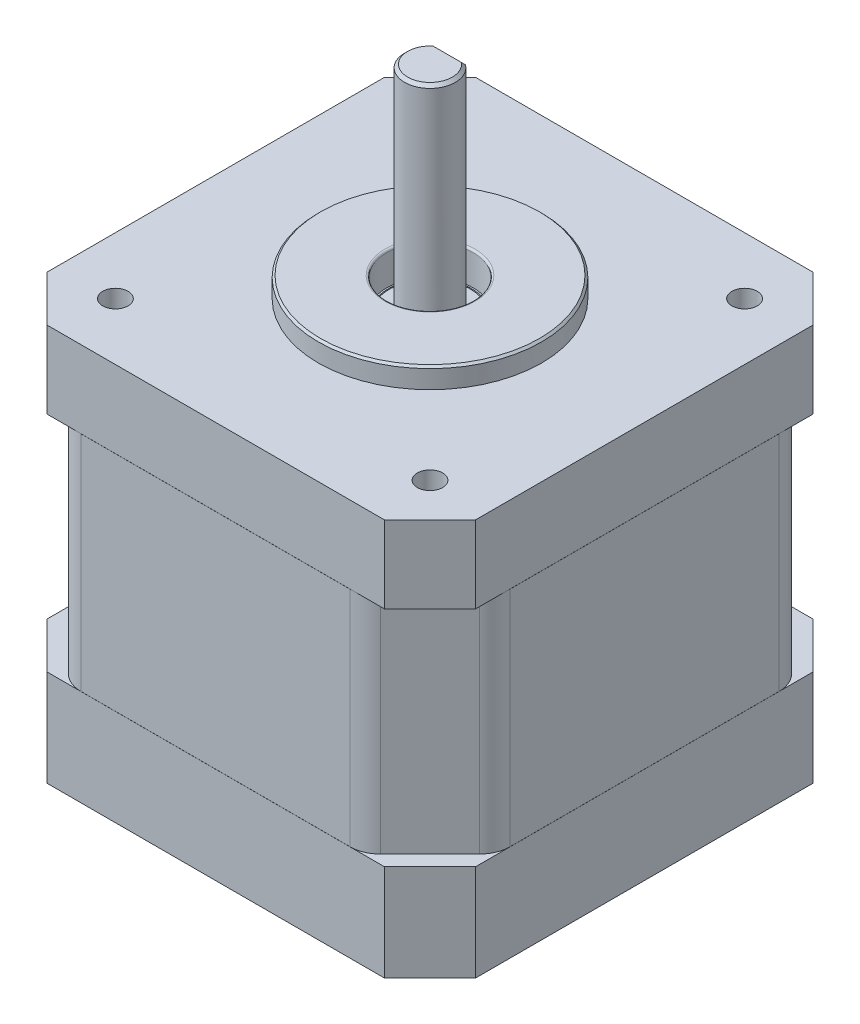
SolidWorks part; units mm, degrees
other "Cámara1"
material "Acero al carbono fundido"
ref_plane "Alzado" through (0, 0, 0) normal (0, 0, 1) x (1, 0, 0)
ref_plane "Planta" through (0, 0, 0) normal (0, 1, 0) x (1, 0, 0)
ref_plane "Vista lateral" through (0, 0, 0) normal (1, 0, 0) x (0, 0, -1)
sketch "Croquis1" plane through (0, 0, 0) normal (0, 1, 0) x (1, 0, 0)
  line L0 (-21.125, 16.625) -> (-16.625, 21.125)
  line L1 (-16.625, -21.125) -> (16.625, -21.125)
  line L2 (-21.125, -16.625) -> (-21.125, 16.625)
  line L3 (-16.625, 21.125) -> (16.625, 21.125)
  line L4 (21.125, -16.625) -> (21.125, 16.625)
  line L5 (-21.125, -21.125) -> (21.125, 21.125) construction
  line L6 (-21.125, 21.125) -> (21.125, -21.125) construction
  line L7 (16.625, 21.125) -> (21.125, 16.625)
  line L8 (-21.125, -16.625) -> (-16.625, -21.125)
  line L9 (16.625, -21.125) -> (21.125, -16.625)
  circle A0 centre (-15.5, 15.5) radius 1
  circle A1 centre (15.5, 15.5) radius 1
  circle A2 centre (-15.5, -15.5) radius 1
  circle A3 centre (15.5, -15.5) radius 1
  point P0 (0, 0)
  dimension "D3" = 2
  dimension "D4" = 31
  dimension "D5" = 31
  dimension "D1" = 42.25
  dimension "D2" = 42.25
extrude "Saliente-Extruir1" add sketch "Croquis1" along normal blind 7.6
sketch "Croquis2" plane through (0, 7.6, 0) normal (0, 1, 0) x (1, 0, 0)
  circle A0 centre (0, 0) radius 11
  dimension "D1" = 22
extrude "Saliente-Extruir2" add sketch "Croquis2" along normal blind 2
chamfer "Chaflán1" distance 0.2 angle 45 1 edges at (0, 9.6, 11)
sketch "Croquis3" plane through (0, 9.6, 0) normal (0, 1, 0) x (1, 0, 0)
  circle A0 centre (0, 0) radius 4.25
  dimension "D1" = 8.5
extrude "Cortar-Extruir1" cut sketch "Croquis3" against normal blind 3.2
fillet "Redondeo1" radius 0.2 1 edges at (0, 9.6, 4.25)
sketch "Croquis4" plane through (0, 6.4, 0) normal (0, 1, 0) x (1, 0, 0)
  circle A0 centre (0, 0) radius 4.1
  circle A1 centre (0, 0) radius 4
  dimension "D1" = 8.2
  dimension "D2" = 8
extrude "Cortar-Extruir2" cut sketch "Croquis4" against normal blind 0.5
sketch "Croquis5" plane through (0, 6.4, 0) normal (0, 1, 0) x (1, 0, 0)
  circle A0 centre (0, 0) radius 2.5
  dimension "D1" = 5
extrude "Saliente-Extruir3" add sketch "Croquis5" along normal blind 21.2
chamfer "Chaflán2" distance 0.3 angle 45 1 edges at (0, 27.6, 2.5)
sketch "Croquis7" plane through (0, 27.6, 0) normal (0, 1, 0) x (1, 0, 0)
  line L0 (0, -2.5) -> (0, 2) construction
  line L1 (-1.5, 2) -> (1.5, 2)
  circle A0 centre (0, 0) radius 2.5 construction
  circle A1 centre (0, 0) radius 2.5 construction
  arc A2 (1.5, 2) -> (-1.5, 2) centre (0, 0) ccw
  point P11 (0, 2)
  dimension "D1" = 4.5
extrude "Cortar-Extruir4" cut sketch "Croquis7" against normal blind 17.2
fillet "Redondeo2" radius 0.1 1 edges at (0, 10.4, -2)
chamfer "Chaflán3" distance 0.3 angle 45 1 edges at (0, 27.6, -2)
sketch "Croquis8" plane through (0, 0, 0) normal (0, -1, 0) x (1, 0, 0)
  line L0 (-14.5, 21.125) -> (14.5, 21.125)
  line L1 (-16.625, 21.125) -> (16.625, 21.125) construction
  line L2 (0, 21.125) -> (0, 0) construction
  line L3 (0, 0) -> (-21.125, 0) construction
  line L4 (-21.125, -16.625) -> (-21.125, 16.625) construction
  line L5 (-21.125, -14.5) -> (-21.125, 14.5)
  line L6 (-21.125, 14.5) -> (-14.5, 21.125)
  line L7 (21.125, -14.5) -> (21.125, 14.5)
  line L8 (-14.5, -21.125) -> (14.5, -21.125)
  line L9 (-21.125, -14.5) -> (-14.5, -21.125)
  line L10 (14.5, -21.125) -> (21.125, -14.5)
  line L11 (21.125, 14.5) -> (14.5, 21.125)
  point P5 (0, 21.125)
  point P14 (-21.125, 0)
  dimension "D1" = 29
  dimension "D2" = 29
extrude "Saliente-Extruir4" add sketch "Croquis8" along normal blind 22
sketch "Croquis9" plane through (0, -22, 0) normal (0, -1, 0) x (1, 0, 0)
  line L8 (16.625, 21.125) -> (-16.625, 21.125)
  line L9 (21.125, 16.625) -> (16.625, 21.125)
  line L10 (21.125, -16.625) -> (21.125, 16.625)
  line L11 (16.625, -21.125) -> (21.125, -16.625)
  line L12 (-16.625, -21.125) -> (16.625, -21.125)
  line L13 (-21.125, -16.625) -> (-16.625, -21.125)
  line L14 (-21.125, 16.625) -> (-21.125, -16.625)
  line L15 (-16.625, 21.125) -> (-21.125, 16.625)
  line L16 (16.625, 21.125) -> (-16.625, 21.125)
  line L17 (21.125, 16.625) -> (16.625, 21.125)
  line L18 (21.125, -16.625) -> (21.125, 16.625)
  line L19 (16.625, -21.125) -> (21.125, -16.625)
  line L20 (-16.625, -21.125) -> (16.625, -21.125)
  line L21 (-21.125, -16.625) -> (-16.625, -21.125)
  line L22 (-21.125, 16.625) -> (-21.125, -16.625)
  line L23 (-16.625, 21.125) -> (-21.125, 16.625)
  dimension "D5" = 0
extrude "Saliente-Extruir5" add sketch "Croquis9" along normal blind 9.5
sketch "Croquis10" plane through (0, -31.5, 0) normal (0, -1, 0) x (1, 0, 0)
  line L0 (-8.175, -21.125) -> (8.175, -21.125)
  line L1 (-16.625, -21.125) -> (16.625, -21.125) construction
  line L2 (0, 0) -> (0, -21.125) construction
  line L3 (8.175, -21.125) -> (8.175, -25.125)
  line L4 (8.175, -25.125) -> (-8.175, -25.125)
  line L5 (-8.175, -25.125) -> (-8.175, -21.125)
  point P5 (0, -21.125)
  dimension "D1" = 16.35
  dimension "D2" = 4
extrude "Saliente-Extruir6" add sketch "Croquis10" against normal blind 3.3
sketch "Croquis11" plane through (0, 6.4, 0) normal (0, 1, 0) x (1, 0, 0)
  circle A0 centre (0, 0) radius 2.575
  circle A1 centre (0, 0) radius 2.5 construction
  circle A2 centre (0, 0) radius 2.5
  dimension "D1" = 5.15
extrude "Cortar-Extruir5" cut sketch "Croquis11" against normal up to surface (0.5 mm away) up to face at (0, 5.9, 4)
sketch "Croquis12" plane through (0, -28.2, 0) normal (0, 1, 0) x (1, 0, 0)
  line L0 (-7, 21.125) -> (7, 21.125)
  line L1 (16.625, 21.125) -> (-16.625, 21.125) construction
  line L2 (-7, 21.125) -> (-7, 25.825)
  line L3 (-7, 25.825) -> (7, 25.825)
  line L4 (7, 25.825) -> (7, 21.125)
  point P5 (0, 21.125)
  dimension "D1" = 14
  dimension "D2" = 4.7
extrude "Saliente-Extruir7" add sketch "Croquis12" along normal blind 1
sketch "Croquis13" plane through (0, -27.2, 0) normal (0, 1, 0) x (1, 0, 0)
  line L0 (16.625, 21.125) -> (-16.625, 21.125) construction
  line L1 (-7.6, 21.125) -> (7.6, 21.125)
  line L2 (7.6, 21.125) -> (7.6, 27.625)
  line L3 (7.6, 27.625) -> (-7.6, 27.625)
  line L4 (-7.6, 27.625) -> (-7.6, 21.125)
  point P0 (0, 21.125)
  point P6 (0, 21.125)
  dimension "D1" = 15.2
  dimension "D2" = 6.5
extrude "Saliente-Extruir8" add sketch "Croquis13" along normal blind 5.5
sketch "Croquis14" plane through (0, 0, -27.625) normal (0, 0, -1) x (-1, 0, 0)
  line L4 (0, -22.7) -> (0, -21.7) construction
  line L5 (7.6, -21.7) -> (-7.6, -21.7) construction
  line L6 (4, -22.7) -> (4, -21.7)
  line L7 (-4, -22.7) -> (-4, -21.7)
  line L8 (-6.6, -26.2) -> (6.6, -26.2)
  line L9 (6.6, -26.2) -> (6.6, -22.7)
  line L10 (6.6, -22.7) -> (-6.6, -22.7)
  line L11 (-6.6, -22.7) -> (-6.6, -26.2)
  line L12 (-6.6, -26.2) -> (6.6, -26.2)
  line L13 (6.6, -26.2) -> (6.6, -22.7)
  line L14 (6.6, -22.7) -> (4, -22.7)
  line L15 (-6.6, -22.7) -> (-6.6, -26.2)
  line L16 (-7.6, -21.7) -> (7.6, -21.7) construction
  line L20 (-4, -21.7) -> (4, -21.7)
  line L21 (-4, -22.7) -> (-6.6, -22.7)
  point P1 (0, -22.7)
  dimension "D2" = 4
  dimension "D1" = 1
  dimension "D3" = 4
extrude "Cortar-Extruir6" cut sketch "Croquis14" against normal blind 4.1
sketch "Croquis15" plane through (0, 0, -23.525) normal (0, 0, -1) x (-1, 0, 0)
  line L0 (-6.6, -24.45) -> (6.6, -24.45) construction
  line L1 (-6.6, -22.7) -> (-6.6, -26.2) construction
  line L2 (6.6, -26.2) -> (6.6, -22.7) construction
  line L3 (-3.0743, -24.2) -> (-2.5743, -24.2)
  line L4 (-4.9643, -24.7) -> (-4.4643, -24.7)
  line L5 (-4.9643, -24.7) -> (-4.9643, -24.2)
  line L6 (-4.9643, -24.2) -> (-4.4643, -24.2)
  line L7 (-4.4643, -24.7) -> (-4.4643, -24.2)
  line L8 (-4.9643, -24.7) -> (-4.4643, -24.2) construction
  line L9 (-4.9643, -24.2) -> (-4.4643, -24.7) construction
  line L10 (-2.5743, -24.7) -> (-2.5743, -24.2)
  line L11 (-3.0743, -24.7) -> (-2.5743, -24.7)
  line L12 (-3.0743, -24.7) -> (-3.0743, -24.2)
  line L13 (-1.1843, -24.2) -> (-0.6843, -24.2)
  line L14 (-0.6843, -24.7) -> (-0.6843, -24.2)
  line L15 (-1.1843, -24.7) -> (-0.6843, -24.7)
  line L16 (-1.1843, -24.7) -> (-1.1843, -24.2)
  line L17 (0.7057, -24.2) -> (1.2057, -24.2)
  line L18 (1.2057, -24.7) -> (1.2057, -24.2)
  line L19 (0.7057, -24.7) -> (1.2057, -24.7)
  line L20 (0.7057, -24.7) -> (0.7057, -24.2)
  line L21 (2.5957, -24.2) -> (3.0957, -24.2)
  line L22 (3.0957, -24.7) -> (3.0957, -24.2)
  line L23 (2.5957, -24.7) -> (3.0957, -24.7)
  line L24 (2.5957, -24.7) -> (2.5957, -24.2)
  line L25 (4.4857, -24.2) -> (4.9857, -24.2)
  line L26 (4.9857, -24.7) -> (4.9857, -24.2)
  line L27 (4.4857, -24.7) -> (4.9857, -24.7)
  line L28 (4.4857, -24.7) -> (4.4857, -24.2)
  point P6 (-4.7143, -24.45)
  dimension "D1" = 0.5
  dimension "D2" = 13.2
  dimension "D3" = 1.8857
  dimension "D4" = 6
extrude "Saliente-Extruir9" add sketch "Croquis15" along normal blind 3.5
chamfer "Chaflán4" distance 0.25 angle 45 24 edges at (-2.8457, -24.7, -27.025) (-2.5957, -24.45, -27.025) (-2.8457, -24.2, -27.025) (-3.0957, -24.45, -27.025) (-4.7357, -24.7, -27.025) (-4.4857, -24.45, -27.025) (-4.7357, -24.2, -27.025) (-4.9857, -24.45, -27.025) (2.8243, -24.7, -27.025) (3.0743, -24.45, -27.025) (2.8243, -24.2, -27.025) (2.5743, -24.45, -27.025) (0.9343, -24.7, -27.025) (1.1843, -24.45, -27.025) (0.9343, -24.2, -27.025) (0.6843, -24.45, -27.025) (-0.9557, -24.7, -27.025) (-0.7057, -24.45, -27.025) (-0.9557, -24.2, -27.025) (-1.2057, -24.45, -27.025) (4.7143, -24.7, -27.025) (4.9643, -24.45, -27.025) (4.7143, -24.2, -27.025) (4.4643, -24.45, -27.025)
sketch "Croquis16" plane through (0, -31.5, 0) normal (0, -1, 0) x (1, 0, 0)
  circle A0 centre (-15.5, 15.5) radius 3
  circle A1 centre (15.5, 15.5) radius 1
  circle A2 centre (15.5, 15.5) radius 1 construction
  circle A3 centre (-15.5, 15.5) radius 1
  circle A4 centre (-15.5, 15.5) radius 1 construction
  circle A5 centre (15.5, -15.5) radius 1
  circle A6 centre (15.5, -15.5) radius 1 construction
  circle A7 centre (-15.5, -15.5) radius 1
  circle A8 centre (-15.5, -15.5) radius 1 construction
  circle A9 centre (15.5, 15.5) radius 3
  circle A10 centre (-15.5, -15.5) radius 3
  circle A11 centre (15.5, -15.5) radius 3
  dimension "D6" = 6
  dimension "D1" = 0
  dimension "D2" = 0
  dimension "D3" = 0
  dimension "D4" = 0
extrude "Cortar-Extruir7" cut sketch "Croquis16" against normal blind 2.5
sketch "Croquis17" plane through (0, -29, 0) normal (0, -1, 0) x (1, 0, 0)
  circle A0 centre (15.5, 15.5) radius 2.75
  circle A1 centre (-15.5, 15.5) radius 2.75
  circle A2 centre (15.5, -15.5) radius 2.75
  circle A3 centre (-15.5, -15.5) radius 2.75
  dimension "D1" = 5.5
  dimension "D2" = 5.5
  dimension "D3" = 5.5
  dimension "D4" = 5.5
extrude "Saliente-Extruir10" add sketch "Croquis17" along normal blind 2.3
fillet "Redondeo3" radius 0.6 4 edges at (15.5, -31.3, -18.25) (-15.5, -31.3, -18.25) (-15.5, -31.3, 12.75) (15.5, -31.3, 12.75)
sketch "Croquis18" plane through (0, -31.3, 0) normal (0, -1, 0) x (1, 0, 0)
  line L0 (16.8789, 14.1211) -> (14.1211, 16.8789) construction
  line L1 (15.5, 15.5) -> (15.5, 17.65) construction
  line L2 (17.3031, 14.5454) -> (16.3485, 15.5)
  line L3 (16.4546, 13.6969) -> (15.5, 14.6515)
  line L4 (14.1211, 14.1211) -> (16.8789, 16.8789) construction
  line L5 (14.5454, 13.6969) -> (15.5, 14.6515)
  line L6 (13.6969, 14.5454) -> (14.6515, 15.5)
  line L7 (16.4546, 17.3031) -> (17.3031, 16.4546)
  line L8 (17.3031, 14.5454) -> (16.4546, 13.6969)
  line L9 (14.5454, 13.6969) -> (13.6969, 14.5454)
  line L10 (13.6969, 16.4546) -> (14.5454, 17.3031)
  line L11 (15.5, 16.3485) -> (14.5454, 17.3031)
  line L12 (16.3485, 15.5) -> (17.3031, 16.4546)
  line L13 (17.3031, 14.5454) -> (14.5454, 17.3031) construction
  line L14 (14.6515, 15.5) -> (13.6969, 16.4546)
  line L15 (14.5454, 13.6969) -> (17.3031, 16.4546) construction
  line L16 (15.5, 16.3485) -> (16.4546, 17.3031)
  line L17 (16.4546, 13.6969) -> (13.6969, 16.4546) construction
  line L18 (-17.3031, 16.4546) -> (-16.4546, 17.3031)
  line L19 (13.6969, 14.5454) -> (16.4546, 17.3031) construction
  line L20 (-15.5, 16.3485) -> (-14.5454, 17.3031)
  line L21 (-14.5454, 13.6969) -> (-15.5, 14.6515)
  line L22 (-16.3485, 15.5) -> (-17.3031, 16.4546)
  line L23 (-13.6969, 14.5454) -> (-14.5454, 13.6969)
  line L24 (-16.4546, 13.6969) -> (-15.5, 14.6515)
  line L25 (-14.5454, 17.3031) -> (-13.6969, 16.4546)
  line L26 (-15.5, 15.5) -> (-15.5, 17.65) construction
  line L27 (-15.5, 16.3485) -> (-16.4546, 17.3031)
  line L28 (-13.6969, 14.5454) -> (-14.6515, 15.5)
  line L29 (-16.4546, 13.6969) -> (-17.3031, 14.5454)
  line L30 (-17.3031, 14.5454) -> (-16.3485, 15.5)
  line L31 (-16.8789, 14.1211) -> (-14.1211, 16.8789) construction
  line L32 (-14.6515, 15.5) -> (-13.6969, 16.4546)
  line L33 (-14.1211, 14.1211) -> (-16.8789, 16.8789) construction
  line L34 (-13.6969, -16.4546) -> (-14.6515, -15.5)
  line L35 (-14.6515, -15.5) -> (-13.6969, -14.5454)
  line L36 (-15.5, -14.6515) -> (-16.4546, -13.6969)
  line L37 (-14.5454, -17.3031) -> (-15.5, -16.3485)
  line L38 (-17.3031, -16.4546) -> (-16.3485, -15.5)
  line L39 (-13.6969, -16.4546) -> (-14.5454, -17.3031)
  line L40 (-15.5, -14.6515) -> (-14.5454, -13.6969)
  line L41 (-16.4546, -17.3031) -> (-15.5, -16.3485)
  line L42 (-16.3485, -15.5) -> (-17.3031, -14.5454)
  line L43 (-16.4546, -17.3031) -> (-17.3031, -16.4546)
  line L44 (-14.1211, -16.8789) -> (-16.8789, -14.1211) construction
  line L45 (-14.5454, -13.6969) -> (-13.6969, -14.5454)
  line L46 (-16.8789, -16.8789) -> (-14.1211, -14.1211) construction
  line L47 (-15.5, -15.5) -> (-15.5, -13.35) construction
  line L48 (-17.3031, -14.5454) -> (-16.4546, -13.6969)
  line L49 (16.3485, -15.5) -> (17.3031, -14.5454)
  line L50 (13.6969, -16.4546) -> (14.6515, -15.5)
  line L51 (16.8789, -16.8789) -> (14.1211, -14.1211) construction
  line L52 (17.3031, -16.4546) -> (16.4546, -17.3031)
  line L53 (14.6515, -15.5) -> (13.6969, -14.5454)
  line L54 (14.5454, -17.3031) -> (15.5, -16.3485)
  line L55 (14.1211, -16.8789) -> (16.8789, -14.1211) construction
  line L56 (15.5, -15.5) -> (15.5, -13.35) construction
  line L57 (14.5454, -17.3031) -> (13.6969, -16.4546)
  line L58 (16.4546, -13.6969) -> (17.3031, -14.5454)
  line L59 (17.3031, -16.4546) -> (16.3485, -15.5)
  line L60 (16.4546, -17.3031) -> (15.5, -16.3485)
  line L61 (15.5, -14.6515) -> (16.4546, -13.6969)
  line L62 (13.6969, -14.5454) -> (14.5454, -13.6969)
  line L63 (15.5, -14.6515) -> (14.5454, -13.6969)
  circle A0 centre (15.5, 15.5) radius 2.15 construction
  point P4 (15.5, 15.5)
  point P8 (15.5, 15.5)
  point P16 (15.5, 15.5)
  point P28 (-15.5, 15.5)
  point P30 (-15.5, 15.5)
  point P37 (-15.5, 15.5)
  point P49 (-15.5, -15.5)
  point P51 (-15.5, -15.5)
  point P58 (-15.5, -15.5)
  point P70 (15.5, -15.5)
  point P72 (15.5, -15.5)
  point P79 (15.5, -15.5)
  dimension "D1" = 3.9
  dimension "D2" = 45
  dimension "D5" = 3.9
  dimension "D6" = 45
  dimension "D9" = 45
  dimension "D8" = 3.9
  dimension "D10" = 3.9
  dimension "D11" = 45
  dimension "D12" = 3.9
  dimension "D13" = 45
  dimension "D14" = 3.9
  dimension "D15" = 45
  dimension "D3" = 0.6
  dimension "D4" = 0.6
  dimension "D7" = 0.6
extrude "Cortar-Extruir8" cut sketch "Croquis18" against normal blind 1.1 draft 10
fillet "Redondeo4" radius 0.2 48 edges at (-17.166, -30.75, -14.5454) (-16.2114, -30.75, -15.5) (-17.166, -30.75, -16.4546) (-16.4546, -30.75, -17.166) (-15.5, -30.75, -16.2114) (-14.5454, -30.75, -17.166) (-13.834, -30.75, -16.4546) (-14.7886, -30.75, -15.5) (-13.834, -30.75, -14.5454) (-14.5454, -30.75, -13.834) (-15.5, -30.75, -14.7886) (-16.4546, -30.75, -13.834) (13.834, -30.75, -14.5454) (14.7886, -30.75, -15.5) (13.834, -30.75, -16.4546) (14.5454, -30.75, -17.166) (15.5, -30.75, -16.2114) (16.4546, -30.75, -17.166) (17.166, -30.75, -16.4546) (16.2114, -30.75, -15.5) (17.166, -30.75, -14.5454) (16.4546, -30.75, -13.834) (15.5, -30.75, -14.7886) (14.5454, -30.75, -13.834) (14.7886, -30.75, 15.5) (13.834, -30.75, 14.5454) (14.5454, -30.75, 13.834) (15.5, -30.75, 14.7886) (16.4546, -30.75, 13.834) (17.166, -30.75, 14.5454) (16.2114, -30.75, 15.5) (17.166, -30.75, 16.4546) (16.4546, -30.75, 17.166) (15.5, -30.75, 16.2114) (14.5454, -30.75, 17.166) (13.834, -30.75, 16.4546) (-15.5, -30.75, 14.7886) (-14.7886, -30.75, 15.5) (-15.5, -30.75, 16.2114) (-16.2114, -30.75, 15.5) (-17.166, -30.75, 14.5454) (-16.4546, -30.75, 13.834) (-14.5454, -30.75, 13.834) (-13.834, -30.75, 14.5454) (-13.834, -30.75, 16.4546) (-14.5454, -30.75, 17.166) (-17.166, -30.75, 16.4546) (-16.4546, -30.75, 17.166)
sketch "Croquis19" plane through (0, -31.5, 0) normal (0, -1, 0) x (1, 0, 0)
  circle A0 centre (0, 0) radius 4.55
  dimension "D1" = 9.1
extrude "Cortar-Extruir9" cut sketch "Croquis19" against normal blind 3.7
sketch "Croquis20" plane through (0, -27.8, 0) normal (0, -1, 0) x (1, 0, 0)
  circle A2 centre (0, 0) radius 5.15
  circle A3 centre (0, 0) radius 5.15
  dimension "D1" = 0.6
extrude "Cortar-Extruir10" cut sketch "Croquis20" along normal blind 2.5
fillet "Redondeo5" radius 3 8 edges
sketch "Croquis24" plane through (0, -22, 0) normal (0, 1, 0) x (1, 0, 0)
  line L8 (14.5, 21.125) -> (-14.5, 21.125)
  line L9 (21.125, 14.5) -> (14.5, 21.125)
  line L10 (21.125, -14.5) -> (21.125, 14.5)
  line L11 (14.5, -21.125) -> (21.125, -14.5)
  line L12 (-14.5, -21.125) -> (14.5, -21.125)
  line L13 (-21.125, -14.5) -> (-14.5, -21.125)
  line L14 (-21.125, 14.5) -> (-21.125, -14.5)
  line L15 (-14.5, 21.125) -> (-21.125, 14.5)
  line L16 (14.5, 21.125) -> (-14.5, 21.125)
  line L17 (21.125, 14.5) -> (14.5, 21.125)
  line L18 (21.125, -14.5) -> (21.125, 14.5)
  line L19 (14.5, -21.125) -> (21.125, -14.5)
  line L20 (-14.5, -21.125) -> (14.5, -21.125)
  line L21 (-21.125, -14.5) -> (-14.5, -21.125)
  line L22 (-21.125, 14.5) -> (-21.125, -14.5)
  line L23 (-14.5, 21.125) -> (-21.125, 14.5)
  dimension "D1" = 0
extrude "Cortar-Extruir-Lámina1" cut sketch "Croquis24" along normal blind 0.01 thin thin type one direction reverse wall 2
sketch "Croquis25" plane through (0, 0, 0) normal (0, -1, 0) x (1, 0, 0)
  line L8 (-14.5, -21.125) -> (14.5, -21.125)
  line L9 (-21.125, -14.5) -> (-14.5, -21.125)
  line L10 (-21.125, 14.5) -> (-21.125, -14.5)
  line L11 (-14.5, 21.125) -> (-21.125, 14.5)
  line L12 (14.5, 21.125) -> (-14.5, 21.125)
  line L13 (21.125, 14.5) -> (14.5, 21.125)
  line L14 (21.125, -14.5) -> (21.125, 14.5)
  line L15 (14.5, -21.125) -> (21.125, -14.5)
  line L16 (-14.5, -21.125) -> (14.5, -21.125)
  line L17 (-21.125, -14.5) -> (-14.5, -21.125)
  line L18 (-21.125, 14.5) -> (-21.125, -14.5)
  line L19 (-14.5, 21.125) -> (-21.125, 14.5)
  line L20 (14.5, 21.125) -> (-14.5, 21.125)
  line L21 (21.125, 14.5) -> (14.5, 21.125)
  line L22 (21.125, -14.5) -> (21.125, 14.5)
  line L23 (14.5, -21.125) -> (21.125, -14.5)
  dimension "D1" = 0
extrude "Cortar-Extruir-Lámina2" cut sketch "Croquis25" along normal blind 0.01 thin thin type one direction reverse wall 2
pattern_linear "MatrizL1" [suppressed] count 60 spacing 0.5 of bodies 124
hole_wizard "M3 Tapped Hole1" positions "Sketch2" profile "Sketch1" tap size "M3" standard "ISO"
sketch "Sketch2" plane through (0, 7.6, 0) normal (0, 1, 0) x (1, 0, 0)
  point P1 (-15.5, 15.5)
  point P4 (15.5, 15.5)
  point P7 (15.5, -15.5)
  point P10 (-15.5, -15.5)
sketch "Sketch1" plane through (-15.5, 7.6, -15.5) normal (1, 0, 0) x (0, 0, 1)
  line L0 (0, 0) -> (0, 8.2511)
  line L1 (0, 8.2511) -> (1.25, 7.5)
  line L2 (1.25, 7.5) -> (1.25, 0)
  line L5 (1.25, 0) -> (0, 0)
  line L10 (0, 8.2511) -> (-1.25, 7.5) construction
  line L11 (0, -6.35) -> (0, 107.95) construction
  dimension "Tap Drill Dia." = 2.5
  dimension "Tap Drill Depth" = 7.5
  dimension "Drill Angle" = 118
cosmetic thread "Hole Thread1" parameters "D1"=6, "D2"=3
cosmetic thread "Hole Thread2" parameters "D1"=6, "D2"=3
cosmetic thread "Hole Thread3" parameters "D1"=6, "D2"=3
cosmetic thread "Hole Thread4" parameters "D1"=6, "D2"=3
